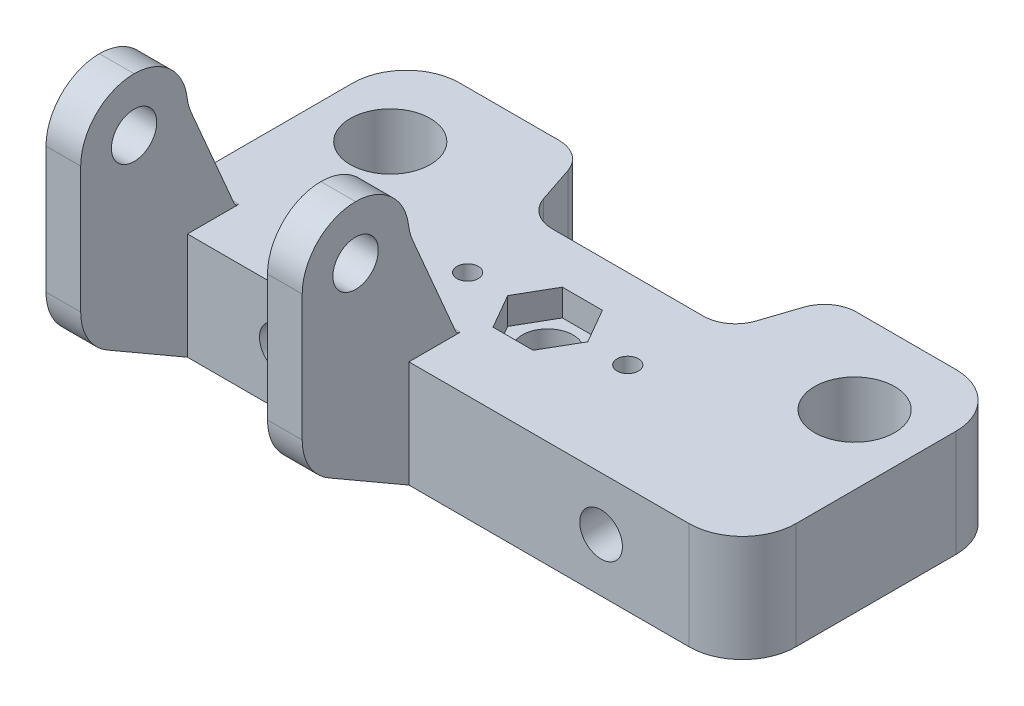
SolidWorks part; units mm, degrees
material "ABS PC"
ref_plane "Front Plane" through (0, 0, 0) normal (0, 0, 1) x (1, 0, 0)
ref_plane "Top Plane" through (0, 0, 0) normal (0, 1, 0) x (1, 0, 0)
ref_plane "Right Plane" through (0, 0, 0) normal (1, 0, 0) x (0, 0, -1)
sketch "Sketch1" plane through (0, 0, 0) normal (0, 1, 0) x (1, 0, 0)
  line L0 (56.5, 0) -> (-56.5, 0)
  line L1 (56.5, 0) -> (56.5, 50)
  line L2 (-56.5, 0) -> (-56.5, 50)
  line L3 (56.5, 50) -> (-56.5, 50)
  dimension "D1" = 113
  dimension "D2" = 50
extrude "Boss-Extrude1" add sketch "Sketch1" along normal blind 20
sketch "Sketch2" plane through (0, 20, 0) normal (0, 1, 0) x (1, 0, 0)
  line L1 (56.5, 0) -> (56.5, 50) construction
  line L3 (56.5, 50) -> (-56.5, 50) construction
  circle A0 centre (-43.5, 34) radius 7.5
  circle A1 centre (43.5, 34) radius 7.5
  circle A2 centre (0, 20) radius 4.75
  circle A3 centre (15, 20) radius 2
  circle A4 centre (-15, 20) radius 2
  dimension "D2" = 56.5
  dimension "D3" = 30
  dimension "D5" = 15
  dimension "D6" = 15
  dimension "D1" = 43.5
  dimension "D4" = 43.5
  dimension "D7" = 14
  dimension "D8" = 9.5
  dimension "D9" = 15
  dimension "D10" = 15
  dimension "D11" = 4
extrude "Cut-Extrude1" cut sketch "Sketch2" against normal through all
sketch "Sketch3" plane through (0, 20, 0) normal (0, 1, 0) x (1, 0, 0)
  line L1 (-3.75, 13.5048) -> (3.75, 13.5048)
  line L2 (3.75, 13.5048) -> (7.5, 20)
  line L3 (7.5, 20) -> (3.75, 26.4952)
  line L4 (3.75, 26.4952) -> (-3.75, 26.4952)
  line L5 (-3.75, 26.4952) -> (-7.5, 20)
  line L6 (-7.5, 20) -> (-3.75, 13.5048)
  circle A0 centre (0, 20) radius 6.4952 construction
  circle A1 centre (0, 20) radius 4.75 construction
  dimension "D1" = 15
extrude "Cut-Extrude2" cut sketch "Sketch3" against normal blind 5
sketch "Sketch5" plane through (0, 0, -50) normal (0, 0, -1) x (-1, 0, 0)
  line L3 (-56.5, 20) -> (-56.5, 0) construction
  line L4 (-56.5, 0) -> (56.5, 0) construction
  circle A0 centre (30, 10) radius 4
  circle A1 centre (-30, 10) radius 4
  dimension "D1" = 8
  dimension "D2" = 60
  dimension "D3" = 26.5
  dimension "D4" = 10
extrude "Cut-Extrude4" cut sketch "Sketch5" against normal through all
sketch "Sketch12" plane through (0, 20, 0) normal (0, 1, 0) x (1, 0, 0)
  line L4 (23.5, 50) -> (18.5, 35)
  line L5 (56.5, 50) -> (-56.5, 50) construction
  line L6 (18.5, 35) -> (-18.5, 35)
  line L7 (-18.5, 35) -> (-23.5, 50)
  line L8 (-23.5, 50) -> (23.5, 50)
  dimension "D2" = 15
  dimension "D3" = 33
  dimension "D4" = 33
  dimension "D5" = 5
  dimension "D6" = 5
extrude "Cut-Extrude6" cut sketch "Sketch12" against normal through all
fillet "Fillet5" radius 6 4 edges at (-23.5, 10, -50) (23.5, 10, -50) (-18.5, 10, -35) (18.5, 10, -35)
sketch "Sketch13" plane through (0, 0, 0) normal (0, 0, 1) x (1, 0, 0)
  line L0 (-47.5, 0) -> (-47.5, 51)
  line L1 (-47.5, 0) -> (-54, 0)
  line L2 (-47.5, 51) -> (-54, 51)
  line L3 (-54, 0) -> (-54, 51)
  line L4 (-56.5, 0) -> (56.5, 0) construction
  line L5 (-12.5, 0) -> (-6, 0)
  line L6 (-12.5, 0) -> (-12.5, 51)
  line L7 (-6, 0) -> (-6, 51)
  line L8 (-12.5, 51) -> (-6, 51)
  circle A1 centre (-30, 10) radius 4 construction
  dimension "D3" = 17.5
  dimension "D4" = 17.5
  dimension "D1" = 51
  dimension "D2" = 6.5
extrude "Boss-Extrude2" add sketch "Sketch13" along normal blind 20
hole_wizard "Ø8.5 (8.5) Diameter Hole1" positions "Sketch15" profile "Sketch14" hole size "Ø8.5" standard "Ansi Metric" end condition through all
sketch "Sketch15" plane through (-6, 0, 0) normal (1, 0, 0) x (0, 0, -1)
  line L0 (0, 20) -> (0, 51) construction
  point P0 (-10, 41)
  dimension "D1" = 10
  dimension "D2" = 21
sketch "Sketch14" plane through (-6, 41, 10) normal (0, 1, 0) x (0, 0, -1)
  line L0 (0, 0) -> (0, 50.5)
  line L1 (0, 50.5) -> (4.25, 50.5)
  line L2 (4.25, 50.5) -> (4.25, 0)
  line L5 (4.25, 0) -> (0, 0)
  line L11 (0, -6.35) -> (0, 107.95) construction
  dimension "Thru Hole Dia." = 8.5
  dimension "Thru Hole Depth" = 50.5
sketch "Sketch16" plane through (-6, 0, 0) normal (1, 0, 0) x (0, 0, -1)
  line L0 (0, 0) -> (-20, 0)
  line L1 (-20, 0) -> (-20, 11.547)
  line L2 (-20, 0) -> (-20, 51) construction
  line L3 (-20, 11.547) -> (0, 0)
  dimension "D1" = 30
extrude "Cut-Extrude7" cut sketch "Sketch16" against normal through all
fillet "Fillet6" radius 10 2 edges at (-50.75, 11.547, 20) (-9.25, 11.547, 20)
fillet "Fillet7" radius 10 4 edges at (-9.25, 51, 0) (-9.25, 51, 20) (-50.75, 51, 20) (-50.75, 51, 0)
sketch "Sketch18" plane through (-54, 0, 0) normal (-1, 0, 0) x (0, 0, 1)
  line L0 (0, 41) -> (0, 20)
  line L1 (0, 20) -> (-9, 20)
  line L2 (-9, 20) -> (0, 41)
  dimension "D1" = 9
extrude "Boss-Extrude3" add sketch "Sketch18" against normal blind 6.5
fillet "Fillet8" radius 10 1 edges at (-50.75, 41, 0)
sketch "Sketch19" plane through (-6, 0, 0) normal (1, 0, 0) x (0, 0, -1)
  line L0 (0, 41) -> (0, 20)
  line L1 (0, 20) -> (9, 20)
  line L2 (9, 20) -> (0, 41)
  dimension "D1" = 9
extrude "Boss-Extrude4" add sketch "Sketch19" against normal blind 6.5
fillet "Fillet9" radius 10 1 edges at (-9.25, 41, 0)
fillet "Fillet10" radius 1 2 edges at (-9.25, 20, -9) (-50.75, 20, -9)
fillet "Fillet11" radius 10 4 edges at (-56.5, 10, 0) (-56.5, 10, -50) (56.5, 10, -50) (56.5, 10, 0)
